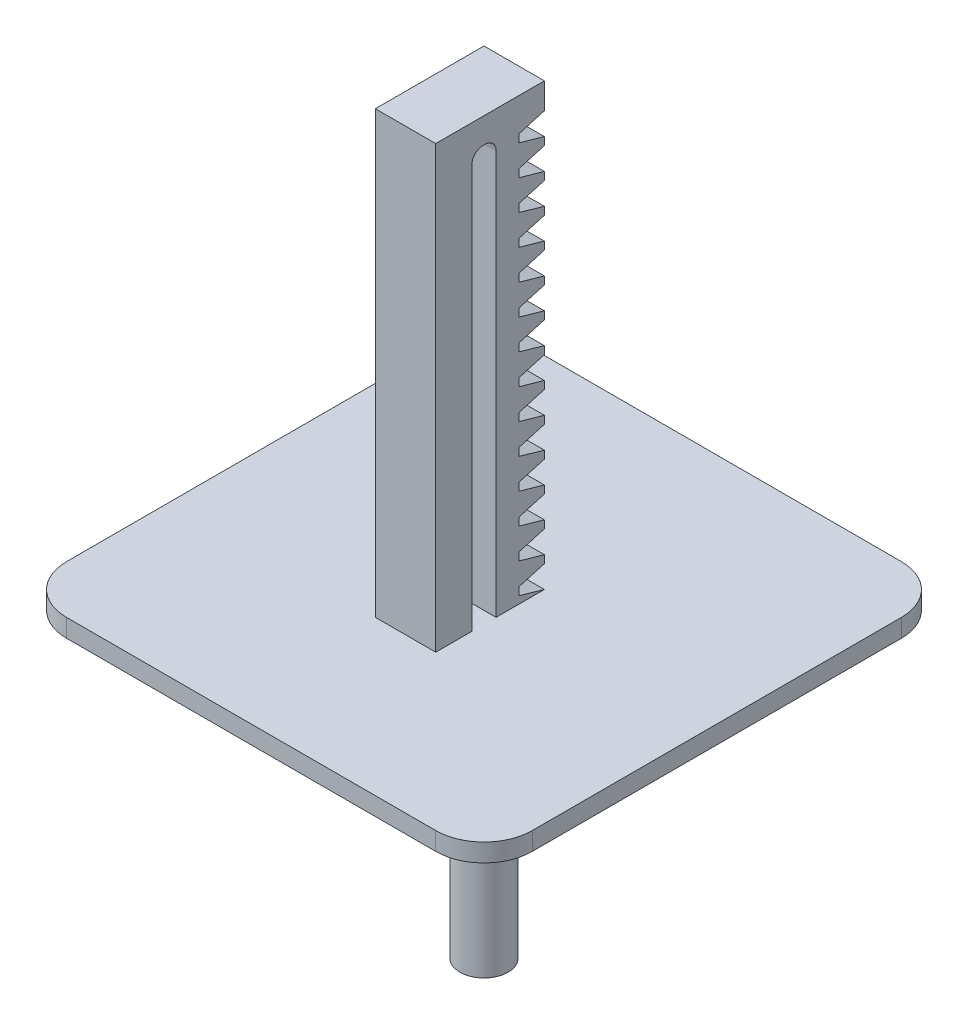
SolidWorks part; units mm, degrees
note: The reader was unsure of these and kept them because the rebuilt part matched: shared geometry of "Szkic1<4>", "Szkic1<5>", "Szkic4<4>".
ref_plane "Płaszczyzna przednia" through (0, 0, 0) normal (0, 0, 1) x (1, 0, 0)
ref_plane "Płaszczyzna górna" through (0, 0, 0) normal (0, 1, 0) x (1, 0, 0)
ref_plane "Płaszczyzna prawa" through (0, 0, 0) normal (1, 0, 0) x (0, 0, -1)
sketch "Szkic1" plane through (0, 0, 0) normal (0, 1, 0) x (1, 0, 0)
  line L0 (0, 19.295) -> (0, -19.295) construction
  line L1 (15.295, -19.295) -> (-15.295, -19.295)
  line L2 (19.295, -15.295) -> (19.295, 15.295)
  line L3 (15.295, 19.295) -> (-15.295, 19.295)
  line L4 (-19.295, -15.295) -> (-19.295, 15.295)
  line L5 (19.295, -19.295) -> (-19.295, 19.295) construction
  line L6 (19.295, 19.295) -> (-19.295, -19.295) construction
  line L7 (-19.295, 0) -> (19.295, 0) construction
  line L11 (2.5, 2.5) -> (-2.5, 2.5)
  line L13 (2.5, -2.5) -> (-2.5, 2.5) construction
  line L14 (2.5, 2.5) -> (-2.5, -2.5) construction
  line L15 (-2.5, -6.5) -> (2.5, -6.5)
  line L17 (-2.5, 2.5) -> (-2.5, -6.5)
  line L18 (2.5, 2.5) -> (2.5, -6.5)
  arc A0 (-15.295, -19.295) -> (-19.295, -15.295) centre (-15.295, -15.295) cw
  arc A1 (15.295, -19.295) -> (19.295, -15.295) centre (15.295, -15.295) ccw
  arc A2 (19.295, 15.295) -> (15.295, 19.295) centre (15.295, 15.295) ccw
  arc A3 (-15.295, 19.295) -> (-19.295, 15.295) centre (-15.295, 15.295) ccw
  circle A8 centre (13.9654, -13.9654) radius 2
  circle A10 centre (-13.9654, 13.9654) radius 2
  point P0 (0, 0)
  point P18 (0, 0)
  point P25 (0, 0)
  point P36 (0, 0)
  dimension "D3" = 4
  dimension "D4" = 5
  dimension "D5" = 9
  dimension "D8" = 19.75
  dimension "D9" = 4
  dimension "D1" = 38.59
  dimension "D2" = 38.59
  dimension "D7" = 39.5
extrude "Dodanie-wyciągnięcie1" add sketch "Szkic1" along normal blind 1.5 contours L3 A3 L4 A0 L1 A1 L2 A2
extrude "Dodanie-wyciągnięcie2" add sketch "Szkic1<4>" along normal blind 38
sketch "Szkic1<4>" plane through (0, 0, 0) normal (0, 1, 0) x (1, 0, 0) same geometry as "Szkic1"
extrude "Dodanie-wyciągnięcie3" add sketch "Szkic1<5>" against normal blind 11
sketch "Szkic1<5>" plane through (0, 0, 0) normal (0, 1, 0) x (1, 0, 0) same geometry as "Szkic1"
sketch "Szkic2" plane through (0, -11, 0) normal (0, 1, 0) x (1, 0, 0)
  circle A0 centre (-14, 14) radius 0.85
  circle A3 centre (14, -14) radius 0.85
  circle A5 centre (14, 14) radius 0.85 [skipped]
  circle A6 centre (-14, -14) radius 0.85 [skipped]
  point P12 (0, 0)
  dimension "D1" = 14
  dimension "D3" = 1.7
  dimension "D2" = 14
  dimension "D4" = 4
extrude "Wytnij-wyciągnięcie3" cut sketch "Szkic2" along normal blind 9
sketch "Szkic4" plane through (-2.5, 0, 0) normal (-1, 0, 0) x (0, 0, 1)
  line L0 (-2.5, 4) -> (-0.4, 4.6)
  line L1 (-2.5, 29) -> (-0.4, 29.6)
  line L2 (-2.5, 3.35) -> (-2.5, 4)
  line L3 (-0.4, 30.25) -> (-0.4, 29.6)
  line L5 (-0.4, 30.25) -> (-2.5, 30.85)
  line L7 (-2.5, 1.5) -> (-0.4, 2.1)
  line L8 (-0.4, 2.75) -> (-2.5, 3.35)
  line L9 (-0.4, 2.75) -> (-0.4, 2.1)
  line L10 (-0.4, 5.25) -> (-0.4, 4.6)
  line L11 (-0.4, 5.25) -> (-2.5, 5.85)
  line L12 (-2.5, 5.85) -> (-2.5, 6.5)
  line L13 (-2.5, 6.5) -> (-0.4, 7.1)
  line L14 (-0.4, 7.75) -> (-0.4, 7.1)
  line L15 (-0.4, 7.75) -> (-2.5, 8.35)
  line L16 (-2.5, 8.35) -> (-2.5, 9)
  line L17 (-2.5, 9) -> (-0.4, 9.6)
  line L18 (-0.4, 10.25) -> (-0.4, 9.6)
  line L19 (-0.4, 10.25) -> (-2.5, 10.85)
  line L20 (-2.5, 10.85) -> (-2.5, 11.5)
  line L21 (-2.5, 11.5) -> (-0.4, 12.1)
  line L22 (-0.4, 12.75) -> (-0.4, 12.1)
  line L23 (-0.4, 12.75) -> (-2.5, 13.35)
  line L24 (-2.5, 13.35) -> (-2.5, 14)
  line L25 (-2.5, 14) -> (-0.4, 14.6)
  line L26 (-0.4, 15.25) -> (-0.4, 14.6)
  line L27 (-0.4, 15.25) -> (-2.5, 15.85)
  line L28 (-2.5, 15.85) -> (-2.5, 16.5)
  line L29 (-2.5, 16.5) -> (-0.4, 17.1)
  line L30 (-0.4, 17.75) -> (-0.4, 17.1)
  line L31 (-0.4, 17.75) -> (-2.5, 18.35)
  line L32 (-2.5, 18.35) -> (-2.5, 19)
  line L33 (-2.5, 19) -> (-0.4, 19.6)
  line L34 (-0.4, 20.25) -> (-0.4, 19.6)
  line L36 (-0.4, 20.25) -> (-2.5, 20.85)
  line L37 (-2.5, 20.85) -> (-2.5, 21.5)
  line L41 (-2.5, 21.5) -> (-0.4, 22.1)
  line L42 (-0.4, 22.75) -> (-0.4, 22.1)
  line L43 (-0.4, 22.75) -> (-2.5, 23.35)
  line L44 (-2.5, 23.35) -> (-2.5, 24)
  line L45 (-2.5, 24) -> (-0.4, 24.6)
  line L46 (-0.4, 25.25) -> (-0.4, 24.6)
  line L47 (-0.4, 25.25) -> (-2.5, 25.85)
  line L48 (-2.5, 25.85) -> (-2.5, 26.5)
  line L49 (-2.5, 26.5) -> (-0.4, 27.1)
  line L50 (-0.4, 27.75) -> (-0.4, 27.1)
  line L51 (-0.4, 27.75) -> (-2.5, 28.35)
  line L52 (-2.5, 28.35) -> (-2.5, 29)
  line L56 (2.6, 35.9) -> (2.4, 35.9)
  line L57 (-2.5, 30.85) -> (-2.5, 31.5)
  line L58 (-2.5, 31.5) -> (-0.4, 32.1)
  line L59 (-0.4, 32.75) -> (-0.4, 32.1)
  line L60 (1.5, 35) -> (1.5, 1.5)
  line L61 (-1.55, 1.5) -> (1.55, 1.5) construction
  line L62 (3.5, 35) -> (3.5, 1.5)
  line L63 (15.295, 1.5) -> (-15.295, 1.5) construction
  line L64 (3.5, 1.5) -> (1.5, 1.5)
  line L65 (6.5, 38) -> (6.5, 1.5) construction
  line L66 (-2.5, 38) -> (6.5, 38) construction
  line L67 (-0.4, 32.75) -> (-2.5, 33.35)
  line L68 (-2.5, 33.35) -> (-2.5, 34)
  line L69 (-2.5, 34) -> (-0.4, 34.6)
  line L70 (-0.4, 35.25) -> (-0.4, 34.6)
  line L71 (-0.4, 35.25) -> (-2.5, 35.85)
  line L72 (-2.5, 35.85) -> (-2.5, 36.5)
  arc A0 (2.6, 35.9) -> (3.5, 35) centre (2.6, 35) cw
  arc A1 (1.5, 35) -> (2.4, 35.9) centre (2.4, 35) cw
  point P34 (-2.5, 30)
  line M104 (-2.5, 1.5) -> (6.5, 1.5)
  dimension "D2" = 0.65
  dimension "D7" = 0.9
  dimension "D1" = 0.6
  dimension "D3" = 14
  dimension "D4" = 2.5
  dimension "D5" = 0.65
  dimension "D6" = 2.1
  dimension "D8" = 4
  dimension "D9" = 2
  dimension "D10" = 3
  dimension "D11" = 3
extrude "Wytnij-wyciągnięcie4" cut sketch "Szkic4" against normal blind 10 and the other way through all contours L7 L9 L8 L2 L0 L10 L11 L12 L13 L14 L15 L16 L17 L18 L19 L20 L21 L22 L23 L24 L25 L26 L27 L28 L29 L30 L31 L32 L33 L34 L36 L37 L41 L42 L43 L44 L45 L46 L47 L48 L49 L50 L51 L52 L1 L3 L5 L57 L58 L59 L67 L68 L69 L70 L71 L72
extrude "Wytnij-wyciągnięcie5" cut sketch "Szkic4<4>" against normal blind 10 contours A1 L60 L62 A0 L56 M104
sketch "Szkic4<4>" plane through (-2.5, 0, 0) normal (-1, 0, 0) x (0, 0, 1) same geometry as "Szkic4"
